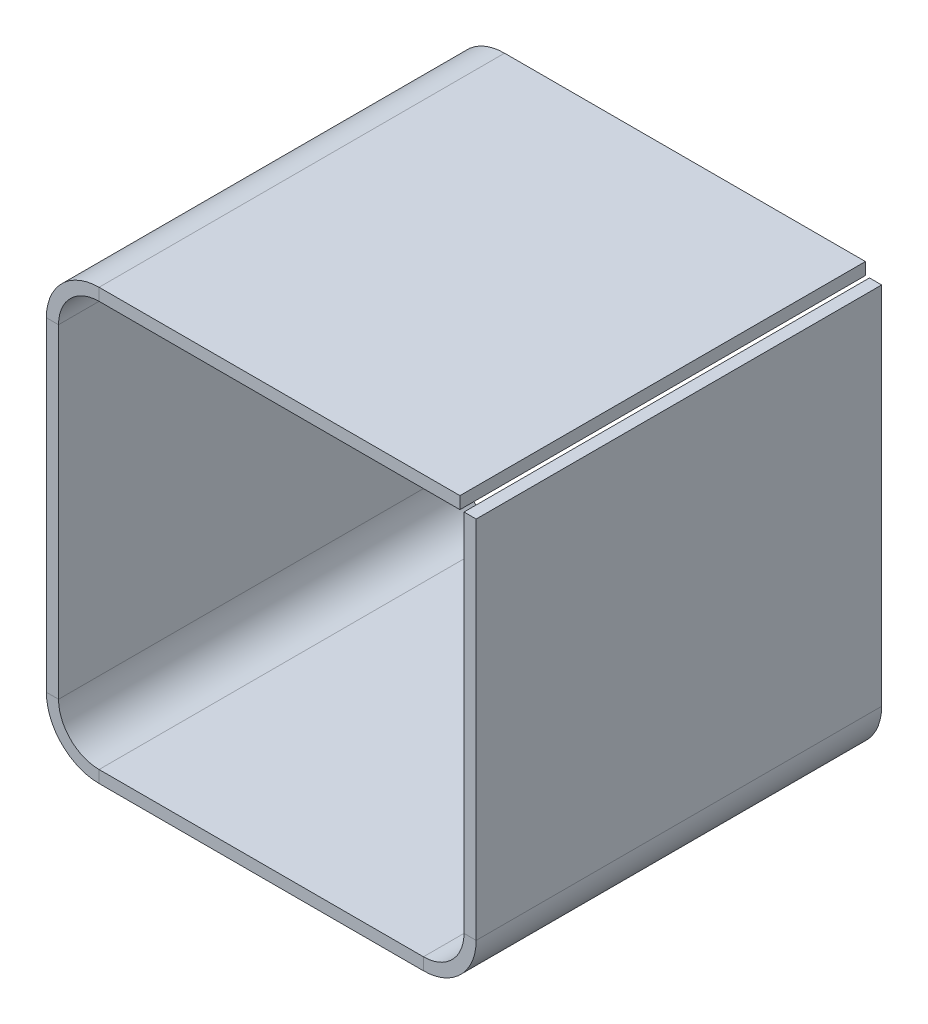
SolidWorks part; units mm, degrees
note: The reader was unsure of these and kept them because the rebuilt part matched: thickness of "Tôle de base pliée1"; bend radius of "Pli de base3".
ref_plane "Plan de face" through (0, 0, 0) normal (0, 0, 1) x (1, 0, 0)
ref_plane "Plan de dessus" through (0, 0, 0) normal (0, 1, 0) x (1, 0, 0)
ref_plane "Plan de droite" through (0, 0, 0) normal (1, 0, 0) x (0, 0, -1)
sketch "Esquisse1" plane through (0, 0, 0) normal (0, 0, 1) x (1, 0, 0)
  line L0 (-44.6906, 100) -> (-44.6906, 0)
  line L1 (-44.6906, 0) -> (55.3094, 0)
  line L2 (55.3094, 0) -> (55.3094, 100)
  line L4 (-44.6906, 100) -> (54.3094, 100)
  dimension "D1" = 100
  dimension "D2" = 100
  dimension "D3" = 100
  dimension "D4" = 90
  dimension "D5" = 90
  dimension "D6" = 99
base flange "Tôle de base pliée1" sketch "Esquisse1" thickness 3 parameters "D1"=10
bend "Pli de base3" bend radius 10 bend angle 90 parameters "D5"=5
bend "Pli de base1" bend radius 10 bend angle 90 parameters "D5"=1
bend "Pli de base2" bend radius 10 bend angle 90 parameters "D5"=2, "D2"=100
sketch "Lignes de pliage1" [suppressed] plane through (0, 0, 0) normal (0, 1, 0) x (1, 0, 0)
sketch "Cube de visualisation1" [suppressed] plane through (0, 0, 0) normal (0, 1, 0) x (1, 0, 0)
sketch "Esquisse6" [suppressed] plane through (-47.6906, 0, 0) normal (-1, 0, 0) x (0, 0, 1)
  line L0 (10, 100.0321) -> (0, 100.0321)
  line L2 (10, 100.0321) -> (10, 98.0321)
  line L3 (0, 100.0321) -> (0, 98.0321)
  line L4 (10, 98.0321) -> (0, 98.0321)
  line L5 (10, 100.0321) -> (0, 98.0321) construction
  line L6 (0, 100.0321) -> (10, 98.0321) construction
  line L8 (100, 99.0321) -> (0, 99.0321) construction
  line L9 (12.5, 94.0321) -> (2.5, 94.0321)
  line L10 (12.5, 94.0321) -> (12.5, 96.0321)
  line L11 (2.5, 94.0321) -> (2.5, 96.0321)
  line L12 (12.5, 96.0321) -> (2.5, 96.0321)
  line L13 (12.5, 94.0321) -> (2.5, 96.0321) construction
  line L14 (2.5, 94.0321) -> (12.5, 96.0321) construction
  line L15 (0, -196.1283) -> (0, 197.0642) construction
  line L16 (0, 99.0321) -> (10, 99.0321) construction
  line L17 (12.5, 104.0321) -> (12.5, 102.0321)
  line L18 (2.5, 104.0321) -> (2.5, 102.0321)
  line L19 (12.5, 104.0321) -> (2.5, 104.0321)
  line L20 (12.5, 102.0321) -> (2.5, 102.0321)
  line L21 (2.5, 103.0321) -> (12.5, 103.0321) construction
  line L22 (10, 106.0321) -> (10, 108.0321)
  line L23 (10, 108.0321) -> (0, 108.0321)
  line L24 (0, 106.0321) -> (0, 108.0321)
  line L25 (10, 106.0321) -> (0, 106.0321)
  line L26 (2.5, 95.0321) -> (12.5, 95.0321) construction
  line L27 (0, 90.0321) -> (0, 92.0321)
  line L28 (10, 92.0321) -> (0, 92.0321)
  line L29 (10, 90.0321) -> (10, 92.0321)
  line L30 (10, 90.0321) -> (0, 90.0321)
  point P1 (5, 99.0321)
  point P9 (7.5, 95.0321)
  dimension "D1" = 10
  dimension "D2" = 2
  dimension "D3" = 10
  dimension "D4" = 2
  dimension "D5" = 2.5
  dimension "D6" = 2
extrude "Enlèv. mat.-Extru.1" [suppressed] cut sketch "Esquisse6" against normal up to next
pattern_linear "Répétition linéaire1" [suppressed] count 9 spacing 11.875 along (0, 0, -1)
pattern_linear "Répétition linéaire3" [suppressed] count 3 spacing 100 along (0, 1, 0)
sheet metal parameters "Tôlerie1" thickness 3 parameters "D1"=10
flat pattern "Etat déplié1" [suppressed]
sketch "Lignes de pliage2" plane through (-44.6906, 0, 0) normal (1, 0, 0) x (0, 0, -1)
  line L0 (0, 0.9679) -> (-100, 0.9679) construction
  line L1 (0, -97.0962) -> (-100, -97.0962) construction
  line L2 (0, 0.9679) -> (-100, 0.9679) construction
  line L3 (0, -97.0962) -> (-100, -97.0962) construction
  line L4 (-100, 99.0321) -> (0, 99.0321) construction
  line L5 (-100, 99.0321) -> (0, 99.0321) construction
sketch3d "Cube de visualisation2" [suppressed]
  line L0 (100, -296.1283, 0) -> (100, 97.0642, 0) construction
  line L1 (0, -296.1283, 0) -> (0, 97.0642, 0) construction
  line L2 (100, -296.1283, 0) -> (0, -296.1283, 0) construction
  line L3 (100, 97.0642, 0) -> (0, 97.0642, 0) construction
bend of the flat pattern "Dépliage-<Pli de base1>1"
bend of the flat pattern "Dépliage-<Pli de base2>1"
bend of the flat pattern "Dépliage-<Pli de base3>1"
